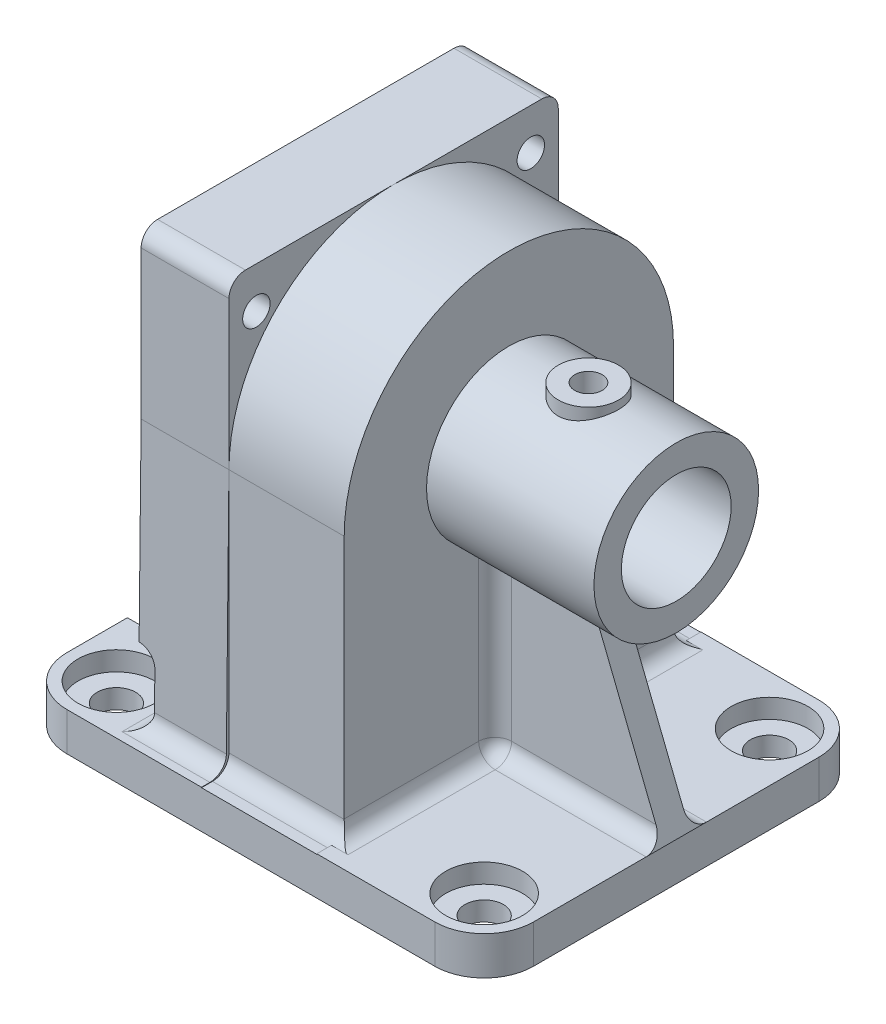
SolidWorks part; units mm, degrees
ref_plane "Front Plane" through (0, 0, 0) normal (0, 0, 1) x (1, 0, 0)
ref_plane "Top Plane" through (0, 0, 0) normal (0, 1, 0) x (1, 0, 0)
ref_plane "Right Plane" through (0, 0, 0) normal (1, 0, 0) x (0, 0, -1)
sketch "Sketch1" plane through (0, 0, 0) normal (0, 1, 0) x (1, 0, 0)
  line L0 (-112.179, 0) -> (237.6607, 0) construction
  line L1 (-67, 70) -> (67, 70)
  line L2 (-85, 52) -> (-85, 30)
  line L3 (-67, -70) -> (67, -70)
  line L4 (85, 52) -> (85, -52)
  line L5 (-85, 70) -> (85, -70) construction
  line L6 (-85, -70) -> (85, 70) construction
  line L7 (-85, 30) -> (-55, 30)
  line L8 (-55, 30) -> (-55, -30)
  line L9 (-55, -30) -> (-85, -30)
  line L10 (-85, -30) -> (-85, -52)
  arc A0 (67, 70) -> (85, 52) centre (67, 52) cw
  arc A1 (-85, -52) -> (-67, -70) centre (-67, -52) ccw
  arc A2 (-67, 70) -> (-85, 52) centre (-67, 52) ccw
  arc A3 (67, -70) -> (85, -52) centre (67, -52) ccw
  point P1 (0, 0)
  dimension "D3" = 18
  dimension "D1" = 140
  dimension "D2" = 170
  dimension "D4" = 30
  dimension "D5" = 60
extrude "Boss-Extrude1" add sketch "Sketch1" along normal blind 14
sketch "Sketch2" plane through (-85, 0, 0) normal (-1, 0, 0) x (0, 0, 1)
  line L2 (-70, 14) -> (70, 14)
  line L3 (-70, 14) -> (-70, 163.2)
  line L4 (-64, 169.2) -> (64, 169.2)
  line L5 (70, 14) -> (70, 163.2)
  arc A0 (64, 169.2) -> (70, 163.2) centre (64, 163.2) cw
  arc A1 (-70, 163.2) -> (-64, 169.2) centre (-64, 163.2) cw
  point P7 (70, 169.2)
  dimension "D3" = 6
  dimension "D1" = 155.2
  dimension "D2" = 140
extrude "Boss-Extrude3" add sketch "Sketch2" against normal blind 135 from offset 35 offset against normal yes
sketch "Sketch4" plane through (-50, 0, 0) normal (-1, 0, 0) x (0, 0, 1)
  line L0 (-100.3488, 109.2) -> (102.9587, 109.2) construction
  line L3 (64, 169.2) -> (-64, 169.2) construction
  line L6 (0, 169.2) -> (0, -25.5299) construction
  circle A0 centre (0, 109.2) radius 50
  dimension "D1" = 100
  dimension "D2" = 60
extrude "Cut-Extrude3" cut sketch "Sketch4" against normal blind 48 from offset 16 offset against normal yes
sketch "Sketch7" plane through (-50, 0, 0) normal (-1, 0, 0) x (0, 0, 1)
  line L0 (-96.434, 109.2) -> (102.7086, 109.2) construction
  line L1 (64, 169.2) -> (-64, 169.2) construction
  line L2 (0, 169.2) -> (0, -16.7145) construction
  circle A0 centre (0, 109.2) radius 45
  point P12 (0, 109.2)
  dimension "D1" = 90
  dimension "D2" = 60
extrude "Cut-Extrude4" cut sketch "Sketch7" against normal blind 16
sketch "Sketch8" plane through (85, 0, 0) normal (1, 0, 0) x (0, 0, -1)
  line L0 (-112.3541, 109.2) -> (112.8761, 109.2) construction
  line L1 (-64, 169.2) -> (64, 169.2) construction
  line L2 (70, 163.2) -> (70, 14) construction
  line L3 (0, 168.8926) -> (0, 0) construction
  line L7 (-70.0017, 109.2) -> (-85.1837, 109.2)
  line L8 (-85.1837, 109.2) -> (-85.1837, 182.0291)
  line L9 (-85.1837, 182.0291) -> (85.1837, 182.0291)
  line L10 (85.1837, 182.0291) -> (85.1837, 109.2)
  line L11 (85.1837, 109.2) -> (70, 109.2)
  arc A0 (-70.0017, 109.2) -> (70, 109.2) centre (-0.0009, 98.3657) cw
  point P4 (-70.0017, 109.2)
  point P17 (-85.1837, 145.6146)
  dimension "D2" = 70.8343
  dimension "D1" = 60
  dimension "D3" = 10.8343
  dimension "D4" = 170.3675
  dimension "D5" = 72.8291
extrude "Cut-Extrude8" cut sketch "Sketch8" against normal blind 103
sketch "Sketch9" plane through (85, 0, 0) normal (1, 0, 0) x (0, 0, -1)
  line L0 (-107.9174, 109.2) -> (107.9174, 109.2) construction
  line L1 (64, 169.2) -> (-0.0009, 169.2) construction
  line L2 (0, 0) -> (0.0048, 169.2) construction
  line L3 (70, 14) -> (-70, 14)
  line L4 (-70, 14) -> (-70, 176.2058)
  line L5 (70, 14) -> (70, 176.2058)
  line L6 (70, 176.2058) -> (-70, 176.2058)
  line L7 (-0.0009, 169.2) -> (-64, 169.2) construction
  arc A0 (70, 109.2) -> (-70, 109.2112) centre (-0.0009, 98.3657) ccw construction
  circle A1 centre (0, 109.2) radius 30
  point P13 (0, 109.2)
  dimension "D2" = 60
  dimension "D1" = 60
  dimension "D3" = 109.2
  dimension "D4" = 7.0058
extrude "Cut-Extrude9" cut sketch "Sketch9" against normal blind 61
sketch "Sketch10" plane through (85, 0, 0) normal (1, 0, 0) x (0, 0, -1)
  circle A0 centre (0, 109.2) radius 20
  dimension "D1" = 40
extrude "Cut-Extrude10" cut sketch "Sketch10" against normal through all
sketch "Sketch11" plane through (0, 0, 0) normal (0, 1, 0) x (1, 0, 0)
  line L0 (53, 58.4132) -> (53, -45.0246) construction
  line L1 (85, -30) -> (85, 30) construction
  line L2 (0, 0) -> (108.9444, 0) construction
  circle A0 centre (53, 0) radius 11
  point P7 (53, 0)
  dimension "D2" = 22
  dimension "D1" = 32
extrude "Boss-Extrude4" add sketch "Sketch11" against normal blind 8 from offset 142.2
sketch "Sketch12" plane through (0, 142.2, 0) normal (0, 1, 0) x (1, 0, 0)
  circle A0 centre (53, 0) radius 5
  dimension "D1" = 10
extrude "Cut-Extrude11" cut sketch "Sketch12" against normal blind 20
sketch "Sketch13" plane through (0, 0, 70) normal (0, 0, 1) x (1, 0, 0)
  line L0 (-93.5632, 39.2) -> (84.4287, 39.2) construction
  line L1 (-18, 169.2) -> (-50, 169.2) construction
  line L2 (-44.194, 33.4971) -> (-44.194, 18.8307)
  line L4 (-50, 14) -> (-50, 163.2) construction
  line L5 (-50, 39.2) -> (-50, 14)
  arc A0 (-50, 39.2) -> (-44.194, 33.2891) centre (-50, 33.3931) cw
  arc A1 (-50, 14) -> (-44.194, 18.8307) centre (-50, 19.9045) ccw
  line M9 (-50, 163.2) -> (-50, 14)
  dimension "D2" = 5.8069
  dimension "D3" = 5.9045
  dimension "D1" = 130
  dimension "D5" = 5.806
extrude "Cut-Extrude12" cut sketch "Sketch13" against normal through all contours A1 L2 A0 M9 region at (-47.2688, 26.5815, 70)
sketch "Sketch16" plane through (24, 0, 0) normal (1, 0, 0) x (0, 0, -1)
  line L0 (-102.9587, 109.2) -> (120.4447, 109.2) construction
  line L1 (-86.2817, 13.8414) -> (-60, 13.8414)
  line L3 (-86.2817, 109.2) -> (-86.2817, 177.1454)
  line L4 (-86.2817, 177.1454) -> (86.2817, 177.1454)
  line L5 (86.2817, 177.1454) -> (86.2817, 109.2)
  line L7 (0, 109.2) -> (0, 156.4753) construction
  line L8 (-0.0009, 169.2) -> (-64, 169.2) construction
  line L9 (-86.2817, 109.2) -> (-86.2817, 13.8414)
  line L10 (86.2817, 109.2) -> (86.2817, 13.8414)
  line L11 (-60, 109.2) -> (-60, 13.8414)
  line L12 (60, 109.2) -> (60, 13.8414)
  line L13 (60, 13.8414) -> (86.2817, 13.8414)
  arc A0 (60, 109.2) -> (-60, 109.2) centre (0, 109.2) ccw
  dimension "D2" = 120
  dimension "D1" = 86.2817
  dimension "D3" = 7.9454
  dimension "D4" = 95.3586
extrude "Cut-Extrude15" cut sketch "Sketch16" against normal up to surface (42 mm away) up to face at (-18, 156.2498, 54.0844)
sketch "Sketch17" plane through (-18, 0, 0) normal (1, 0, 0) x (0, 0, -1)
  line L0 (-60, 109.2) -> (-60, 191.0889)
  line L1 (-60, 191.0889) -> (-82.3751, 191.0889)
  line L2 (-82.3751, 191.0889) -> (-82.3751, 14)
  line L3 (-60, 109.2) -> (-61, 14)
  line L4 (-52, 14) -> (-70, 14) construction
  line L5 (-61, 14) -> (-82.3751, 14)
  line L6 (0, 109.2) -> (0, 182.136) construction
  line L7 (-0.0009, 169.2) -> (-64, 169.2) construction
  line L8 (61, 14) -> (82.3751, 14)
  line L9 (60, 109.2) -> (61, 14)
  line L10 (82.3751, 191.0889) -> (82.3751, 14)
  line L11 (60, 191.0889) -> (82.3751, 191.0889)
  line L12 (60, 109.2) -> (60, 191.0889)
  dimension "D1" = 22.3751
  dimension "D2" = 21.8889
extrude "Cut-Extrude16" cut sketch "Sketch17" against normal blind 103
sketch "Sketch18" plane through (0, 0, 0) normal (0, 0, 1) x (1, 0, 0)
  line L0 (85, 14) -> (59, 79.2)
  line L3 (24, 79.2) -> (85, 79.2) construction
  line L4 (24, 109.2) -> (24, 14) construction
  dimension "D1" = 35
rib "Rib14" sketch "Sketch18" sketch "Sketch18" thickness 10 extrusion direction parallel to sketch draft on no parameters "D1"=10
fillet "Fillet3" radius 6 4 edges at (-34, 14, -61) (-34, 14, 61) (-34, 169.2, -60) (-34, 169.2, 60)
fillet "Fillet5" radius 6 2 edges at (3, 13.8414, -60) (3, 13.8414, 60)
fillet "Fillet6" radius 6 2 edges at (24, 14, 34.8147) (24, 14, -34.8147)
fillet "Fillet7" radius 6 6 edges at (24, 49.8098, 5) (25.7574, 15.7574, 5) (24, 49.8098, -5) (25.7574, 15.7574, -5) (57.5, 14, 5) (57.5, 14, -5)
sketch "Sketch19" plane through (-50, 0, 0) normal (-1, 0, 0) x (0, 0, 1)
  line L0 (0, 169.2) -> (0, 39.2) construction
  line L1 (54, 169.2) -> (-54, 169.2) construction
  line L2 (-60.7353, 39.2) -> (60.7353, 39.2) construction
  line L3 (-60, 109.2) -> (60, 109.2) construction
  line L4 (-60, 163.2) -> (-60, 109.2) construction
  circle A0 centre (-50, 154.2) radius 5
  circle A1 centre (-50, 64.2) radius 5
  circle A2 centre (50, 64.2) radius 5
  circle A3 centre (50, 154.2) radius 5
  dimension "D1" = 10
  dimension "D2" = 15
  dimension "D3" = 10
extrude "Cut-Extrude17" cut sketch "Sketch19" against normal blind 48
sketch "Sketch20" plane through (0, 14, 0) normal (0, 1, 0) x (1, 0, 0)
  line L0 (-85, 52) -> (-67, 52) construction
  circle A0 centre (-67, 52) radius 7
  circle A1 centre (67, 52) radius 7
  circle A2 centre (67, -52) radius 7
  circle A3 centre (-67, -52) radius 7
  point P13 (0, 0)
  dimension "D2" = 14
  dimension "D3" = 14
  dimension "D4" = 14
  dimension "D5" = 14
  dimension "D1" = 18
extrude "Cut-Extrude20" cut sketch "Sketch20" against normal blind 20 contours A1 | A2 | A3 | A0 region at (67, 14, -52) region at (67, 14, 52) region at (-67, 14, 52)
sketch "Sketch21" plane through (0, 14, 0) normal (0, 1, 0) x (1, 0, 0)
  circle A0 centre (-67, 52) radius 14
  circle A1 centre (67, 52) radius 14
  circle A2 centre (67, -52) radius 14
  circle A3 centre (-67, -52) radius 14
  dimension "D1" = 28
extrude "Cut-Extrude21" cut sketch "Sketch21" against normal blind 7
